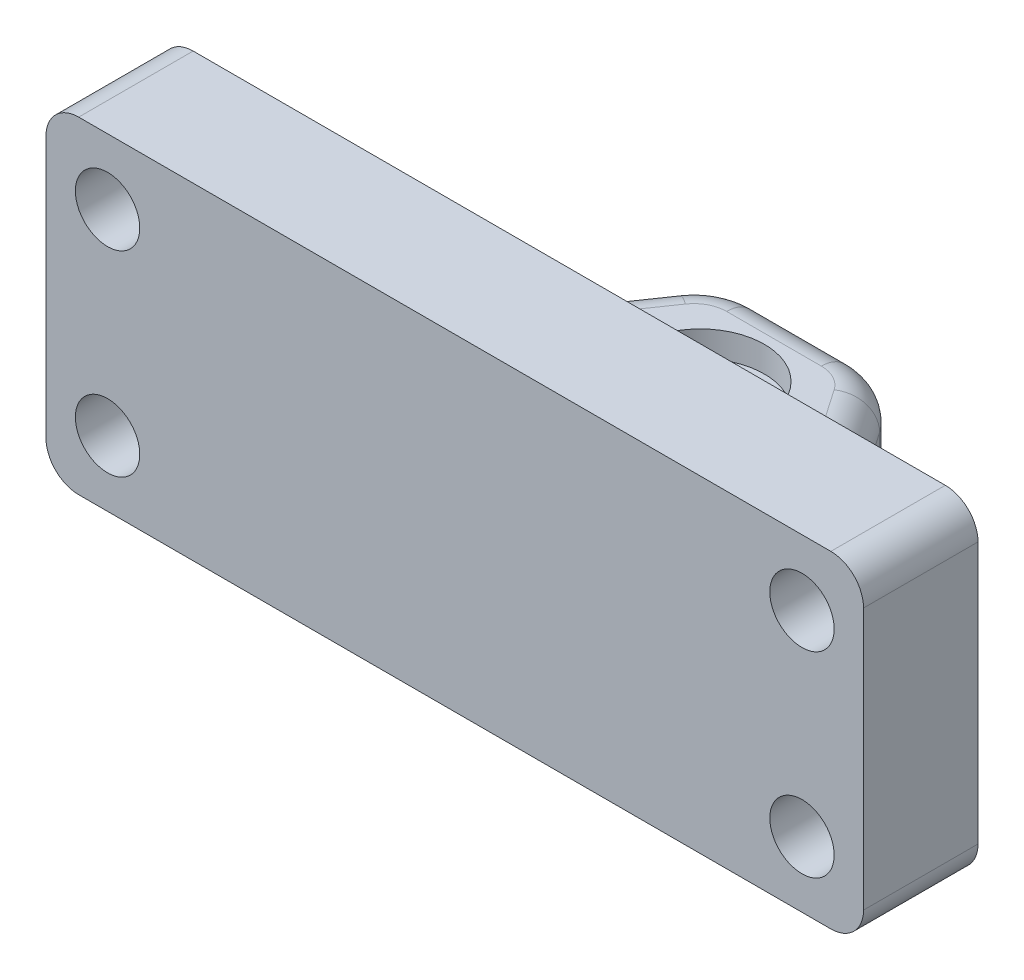
SolidWorks part; units mm, degrees
material "ABS"
ref_plane "Front Plane" through (0, 0, 0) normal (0, 0, 1) x (1, 0, 0)
ref_plane "Top Plane" through (0, 0, 0) normal (0, 1, 0) x (1, 0, 0)
ref_plane "Right Plane" through (0, 0, 0) normal (1, 0, 0) x (0, 0, -1)
sketch "Sketch1" plane through (0, 0, 0) normal (0, 1, 0) x (1, 0, 0)
  line L0 (31.75, 0) -> (-31.75, 0)
  line L1 (-31.75, 0) -> (-31.75, 8.89)
  line L2 (-31.75, 8.89) -> (-19.05, 8.89)
  line L3 (-19.05, 8.89) -> (-6.35, 27.3328)
  line L4 (-6.35, 27.3328) -> (6.35, 27.3328)
  line L5 (6.35, 27.3328) -> (19.05, 8.89)
  line L6 (19.05, 8.89) -> (31.75, 8.89)
  line L7 (31.75, 8.89) -> (31.75, 0)
  circle A0 centre (0, 19.05) radius 4.375
  point P4 (0, 0)
  point P12 (0, 27.3328)
  dimension "D3" = 8.75
  dimension "D1" = 19.05
  dimension "D2" = 63.5
  dimension "D4" = 12.7
  dimension "D5" = 8.89
  dimension "D6" = 12.7
extrude "Boss-Extrude1" add sketch "Sketch1" along normal blind 25.4
sketch "Sketch2" plane through (0, 25.4, 0) normal (0, 1, 0) x (1, 0, 0)
  line L0 (-19.05, 8.89) -> (19.05, 8.89)
  line L8 (-31.75, 8.89) -> (-31.75, 0)
  line L9 (-31.75, 0) -> (31.75, 0)
  line L10 (31.75, 0) -> (31.75, 8.89)
  line L11 (31.75, 8.89) -> (19.05, 8.89)
  line L12 (19.05, 8.89) -> (6.35, 27.3328)
  line L13 (6.35, 27.3328) -> (-6.35, 27.3328)
  line L14 (-6.35, 27.3328) -> (-19.05, 8.89)
  line L15 (-19.05, 8.89) -> (-31.75, 8.89)
  line L20 (19.05, 8.89) -> (6.35, 27.3328)
  line L21 (6.35, 27.3328) -> (-6.35, 27.3328)
  line L22 (-6.35, 27.3328) -> (-19.05, 8.89)
  dimension "D1" = 0
extrude "Cut-Extrude1" cut sketch "Sketch2" against normal blind 12.7
sketch "Sketch3" plane through (0, 12.7, 0) normal (0, 1, 0) x (1, 0, 0)
  circle A0 centre (0, 19.05) radius 5
  dimension "D1" = 10
extrude "Cut-Extrude2" cut sketch "Sketch3" against normal blind 2
sketch "Sketch4" plane through (0, 0, -8.89) normal (0, 0, -1) x (-1, 0, 0)
  line L0 (19.05, 12.7) -> (-19.05, 12.7) construction
  line L1 (-26.9684, 5.0901) -> (26.9684, 5.0901) construction
  line L2 (-26.9684, 5.0901) -> (-26.9684, 20.3099) construction
  line L3 (-26.9684, 20.3099) -> (26.9684, 20.3099) construction
  line L4 (26.9684, 5.0901) -> (26.9684, 20.3099) construction
  line L5 (-26.9684, 5.0901) -> (26.9684, 20.3099) construction
  line L6 (-26.9684, 20.3099) -> (26.9684, 5.0901) construction
  circle A0 centre (26.9684, 5.0901) radius 2.5
  circle A1 centre (26.9684, 20.3099) radius 2.5
  circle A2 centre (-26.9684, 5.0901) radius 2.5
  circle A3 centre (-26.9684, 20.3099) radius 2.5
  point P0 (0, 12.7)
  dimension "D1" = 5
extrude "Cut-Extrude3" cut sketch "Sketch4" against normal through all
fillet "Fillet1" radius 5.08 5 edges at (6.35, 6.35, -27.3328) (-6.35, 6.35, -27.3328) (19.05, 6.35, -8.89) (0, 12.7, -8.89) (-19.05, 6.35, -8.89)
fillet "Fillet2" radius 2.54 13 edges at (19.3565, 15.4167, -9.4732) (16.5907, 12.9292, -12.4614) (11.708, 12.7, -19.552) (6.0435, 12.7, -26.7496) (0, 12.7, -27.3328) (-6.0435, 12.7, -26.7496) (-19.3565, 15.4167, -9.4732) (-16.5907, 12.9292, -12.4614) (31.75, 0, -4.445) (31.75, 25.4, -4.445) (-31.75, 0, -4.445) (-31.75, 25.4, -4.445) (-11.708, 12.7, -19.552)
chamfer "Chamfer1" distance 1.016 angle 45 4 edges at (24.4684, 20.3099, -8.89) (-29.4684, 20.3099, -8.89) (-29.4684, 5.0901, -8.89) (24.4684, 5.0901, -8.89)
